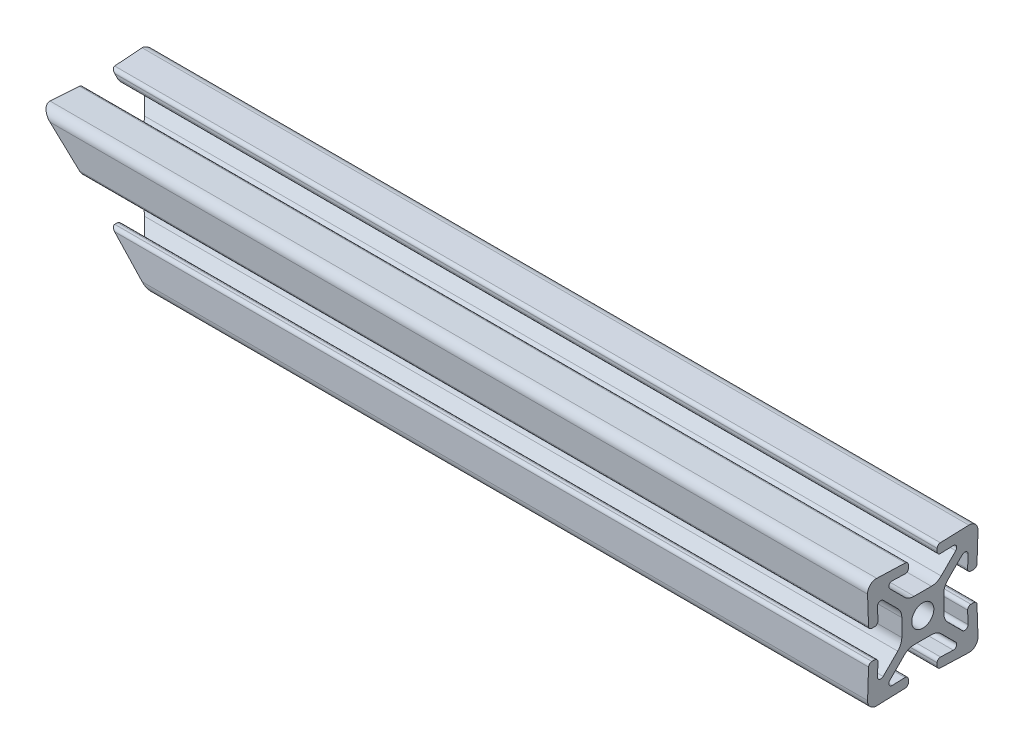
SolidWorks part; units mm, degrees
ref_plane "Front Plane" through (0, 0, 0) normal (0, 0, 1) x (1, 0, 0)
ref_plane "Top Plane" through (0, 0, 0) normal (0, 1, 0) x (1, 0, 0)
ref_plane "Right Plane" through (0, 0, 0) normal (1, 0, 0) x (0, 0, -1)
sketch "Sketch1" plane through (0, 0, 0) normal (1, 0, 0) x (0, 0, -1)
  line L0 (0, -12.7) -> (0, 12.7) construction
  line L1 (-7.874, 12.7) -> (7.874, 12.7) construction
  line L2 (-12.7, 0) -> (12.7, 0) construction
  line L3 (-7.874, 12.7) -> (-7.874, 4.826) construction
  line L4 (-3.302, 12.7) -> (3.302, 12.7) construction
  line L5 (-12.7, -12.7) -> (12.7, -12.7) construction
  line L6 (-12.7, 12.7) -> (12.7, 12.7) construction
  circle A0 centre (0, 0) radius 2.54 construction
  point P7 (0, 12.7)
  point P10 (0, 0)
  point P13 (0, 0)
  point P16 (0, 12.7)
  point P17 (-3.302, 12.7)
  point P18 (3.302, 12.7)
  point P21 (0, -12.7)
  point P24 (0, 12.7)
  dimension "Center Hole Diameter" = 5.08
  dimension "Rail Width" = 25.4
  dimension "Rail Height" = 25.4
  dimension "T-Slot Depth" = 7.874
  dimension "D1" = 15.748
  dimension "T-Slot Width" = 6.604
  dimension "D2" = 12.7
sketch "Sketch2" plane through (0, 0, 0) normal (0, 0, 1) x (1, 0, 0)
  line L0 (-95.0631, 0) -> (95.0631, 0) construction
  line L1 (0, 0) -> (0, 26.104) construction
  line L2 (95.0631, -12.7) -> (95.0631, 12.7) construction
  line L3 (-95.0631, -12.7) -> (-95.0631, 12.7) construction
  point P3 (-56.9631, 0)
  point P8 (0, 0)
  point P9 (56.9631, 0)
  point P12 (95.0631, 0)
  point P15 (-95.0631, 0)
  dimension "Length" = 190.1261
  dimension "D1" = 38.1
  dimension "D2" = 25.4
sketch "Sketch3" plane through (0, 0, 0) normal (1, 0, 0) x (0, 0, -1)
  line L0 (0, 4.826) -> (1.9842, 4.826)
  line L1 (0, -12.7) -> (0, 12.7) construction
  line L2 (4.2293, 5.7559) -> (7.5866, 9.1132)
  line L6 (7.0212, 10.4136) -> (4.0906, 10.3112)
  line L7 (3.302, 11.0728) -> (3.302, 11.7082)
  line L8 (-7.874, 12.7) -> (7.874, 12.7) construction
  line L10 (0, 0) -> (12.7, 12.7) construction
  line L13 (0, 4.826) -> (0, 2.54)
  line L14 (4.826, 0) -> (2.54, 0)
  line L31 (4.826, 0) -> (4.826, 1.9842)
  line L32 (4.0374, 12.4697) -> (10.5971, 12.6988)
  line L33 (-12.7, 0) -> (12.7, 0) construction
  line L34 (-12.7, 12.7) -> (12.7, 12.7) construction
  line L35 (5.7559, 4.2293) -> (9.1132, 7.5866)
  line L36 (0, 12.7) -> (12.7, 12.7) construction
  line L37 (12.7, 12.7) -> (12.7, 8.0234) construction
  line L38 (11.0728, 3.302) -> (11.7082, 3.302)
  line L39 (10.4136, 7.0212) -> (10.3112, 4.0906)
  line L40 (12.6988, 10.5971) -> (12.4697, 4.0374)
  arc A0 (2.54, 0) -> (0, 2.54) centre (0, 0) ccw
  arc A1 (1.9842, 4.826) -> (4.2293, 5.7559) centre (1.9842, 8.001) ccw
  circle A2 centre (0, 0) radius 2.54 construction
  arc A7 (3.302, 11.7082) -> (4.0374, 12.4697) centre (4.064, 11.7082) cw
  arc A8 (4.0906, 10.3112) -> (3.302, 11.0728) centre (4.064, 11.0728) cw
  arc A14 (4.826, 1.9842) -> (5.7559, 4.2293) centre (8.001, 1.9842) cw
  arc A16 (10.5971, 12.6988) -> (12.6988, 10.5971) centre (10.668, 10.668) cw
  arc A17 (7.0212, 10.4136) -> (7.5866, 9.1132) centre (7.0478, 9.652) cw
  arc A18 (10.4136, 7.0212) -> (9.1132, 7.5866) centre (9.652, 7.0478) ccw
  arc A19 (10.3112, 4.0906) -> (11.0728, 3.302) centre (11.0728, 4.064) ccw
  arc A20 (11.7082, 3.302) -> (12.4697, 4.0374) centre (11.7082, 4.064) ccw
  point P37 (3.2994, 4.826)
  point P49 (12.7, 3.302)
  point P52 (3.302, 12.7)
  point P55 (3.302, 10.2837)
  dimension "D4" = 3.175
  dimension "D9" = 2.159
  dimension "D12" = 0.762
  dimension "D3" = 2.032
  dimension "D8" = 0.762
  dimension "D2" = 45
  dimension "D5" = 2
  dimension "D6" = 45
  dimension "D7" = 2.159
extrude "Boss-Extrude1" add sketch "Sketch3" against normal up to vertex (95.0631 mm away) and the other way up to vertex (95.0631 mm away) up to point (-95.0631, 0, 0) other way up to point (95.0631, 0, 0)
mirror "Mirror1" about plane through (0, 0, 0) normal (0, 1, 0) of bodies 104
mirror "Mirror2" about plane through (0, 0, 0) normal (0, 0, 1) of bodies 105
sketch "Sketch4" plane through (-95.0631, 0, 0) normal (-1, 0, 0) x (0, 0, 1)
  line L0 (10.5971, 12.6988) -> (13.9842, 12.6988)
  line L1 (12.6988, 10.5971) -> (12.6988, 12.6988)
  line L2 (12.6988, 12.6988) -> (10.5971, 12.6988)
  line L3 (12.6988, -10.5971) -> (12.6988, -12.7)
  line L4 (12.6988, -12.7) -> (10.668, -12.7)
  arc A0 (10.5971, -12.6988) -> (12.6988, -10.5971) centre (10.668, -10.668) ccw construction
ref_plane "Plane1" through (0, 0, 12.6988) normal (0, 0, -1) x (-1, 0, 0)
sketch "Sketch5" plane through (0, 0, 12.6988) normal (0, 0, -1) x (-1, 0, 0)
  line L0 (95.0631, -12.7) -> (69.6631, -12.7)
  line L1 (69.6631, -12.7) -> (95.0631, 12.7)
  dimension "D1" = 25.4
extrude "Cut-Extrude1" cut sketch "Sketch5" against normal through all and the other way through all flip side to cut
equation "\"D1@Sketch2\"=\"Rail Height@Sketch1\"*1.5"
equation "\"D2@Sketch2\"=\"Rail Height@Sketch1\""
